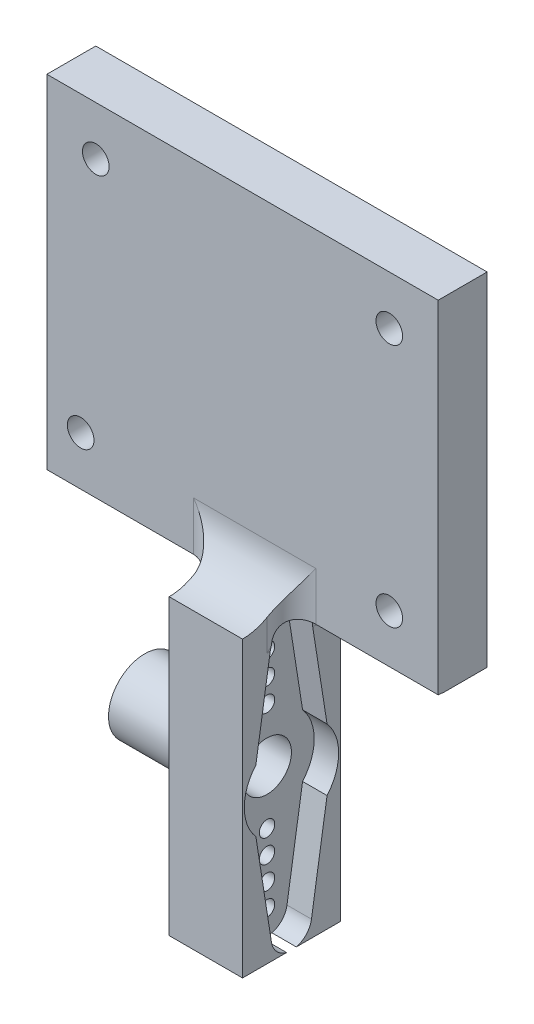
SolidWorks part; units mm, degrees
ref_plane "Front Plane" through (0, 0, 0) normal (0, 0, 1) x (1, 0, 0)
ref_plane "Top Plane" through (0, 0, 0) normal (0, 1, 0) x (1, 0, 0)
ref_plane "Right Plane" through (0, 0, 0) normal (1, 0, 0) x (0, 0, -1)
sketch "Sketch2" plane through (0, 0, 0) normal (1, 0, 0) x (0, 0, -1)
  line L0 (0, 0) -> (36.5165, 0) construction
  line L1 (-6.35, -19.05) -> (6.35, -19.05)
  line L2 (-6.35, -19.05) -> (-6.35, 19.05)
  line L3 (-6.35, 19.05) -> (6.35, 19.05)
  line L4 (6.35, -19.05) -> (6.35, 19.05)
  line L5 (-6.35, -19.05) -> (6.35, 19.05) construction
  line L6 (-6.35, 19.05) -> (6.35, -19.05) construction
  circle A0 centre (0, 0) radius 3.175
  point P0 (0, 0)
  point P8 (0, 0)
  dimension "D3" = 6.35
  dimension "D1" = 12.7
  dimension "D2" = 38.1
extrude "Boss-Extrude1" add sketch "Sketch2" along normal blind 9.525
sketch "Sketch3" plane through (0, 0, 0) normal (-1, 0, 0) x (0, 0, 1)
  circle A0 centre (0, 0) radius 4.699
  dimension "D1" = 9.398
extrude "Boss-Extrude2" add sketch "Sketch3" along normal blind 9.525
ref_plane "Plane1" through (3.175, 0, 0) normal (1, 0, 0) x (0, 0, -1)
sketch "Sketch6" plane through (3.175, 0, 0) normal (1, 0, 0) x (0, 0, -1)
  line L0 (6.35, 19.05) -> (-6.35, 19.05) construction
  line L1 (0, 19.05) -> (6.35, 19.05)
  line L2 (0, 19.05) -> (0, 63.5)
  line L3 (0, 63.5) -> (6.35, 63.5)
  line L4 (6.35, 19.05) -> (6.35, 63.5)
  point P4 (0, 0)
  point P5 (0, 0)
  point P7 (0, 19.05)
  dimension "D1" = 6.35
  dimension "D2" = 63.5
extrude "Boss-Extrude3" add sketch "Sketch6" along normal mid plane 50.8
fillet "Fillet1" radius 6.35 1 edges at (4.7625, 19.05, 0)
fillet "Fillet4" radius 3.175 4 edges at (0, 22.225, 0) (9.525, 22.225, 0) (9.525, 19.05, -3.175) (0, 19.05, -3.175)
sketch "Sketch7" plane through (9.525, 0, 0) normal (1, 0, 0) x (0, 0, -1)
  line L0 (2.5951, -16.9078) -> (4.6198, -4.0247)
  line L1 (4.6198, 4.0247) -> (2.5951, 16.9078)
  line L2 (-2.5951, 16.9078) -> (-4.6198, 4.0247)
  line L3 (-4.6198, -4.0247) -> (-2.5951, -16.9078)
  line L4 (2.4697, -16.8881) -> (4.5, -3.9686)
  line L5 (-4.5, -3.9686) -> (-2.4697, -16.8881)
  line L6 (-2.4697, 16.8881) -> (-4.5, 3.9686)
  line L7 (4.5, 3.9686) -> (2.4697, 16.8881)
  line L8 (2.4697, -16.8881) -> (4.5, -3.9686) construction
  line L9 (-4.5, -3.9686) -> (-2.4697, -16.8881) construction
  line L10 (-2.4697, 16.8881) -> (-4.5, 3.9686) construction
  line L11 (4.5, 3.9686) -> (2.4697, 16.8881) construction
  arc A0 (4.6198, -4.0247) -> (4.6198, 4.0247) centre (0, 0) ccw
  arc A1 (2.5951, 16.9078) -> (-2.5951, 16.9078) centre (0, 16.5) ccw
  arc A2 (-4.6198, 4.0247) -> (-4.6198, -4.0247) centre (0, 0) ccw
  arc A3 (-2.5951, -16.9078) -> (2.5951, -16.9078) centre (0, -16.5) ccw
  arc A4 (4.5, -3.9686) -> (4.5, 3.9686) centre (0, 0) ccw
  arc A5 (-2.4697, -16.8881) -> (2.4697, -16.8881) centre (0, -16.5) ccw
  arc A6 (-4.5, 3.9686) -> (-4.5, -3.9686) centre (0, 0) ccw
  arc A7 (2.4697, 16.8881) -> (-2.4697, 16.8881) centre (0, 16.5) ccw
  arc A8 (4.5, -3.9686) -> (4.5, 3.9686) centre (0, 0) ccw construction
  arc A9 (-2.4697, -16.8881) -> (2.4697, -16.8881) centre (0, -16.5) ccw construction
  arc A10 (-4.5, 3.9686) -> (-4.5, -3.9686) centre (0, 0) ccw construction
  arc A11 (2.4697, 16.8881) -> (-2.4697, 16.8881) centre (0, 16.5) ccw construction
  dimension "D2" = 0.127
sketch "Sketch8" plane through (9.525, 0, 0) normal (1, 0, 0) x (0, 0, -1)
  circle A0 centre (0, -16) radius 0.75 construction
  circle A3 centre (0, -13) radius 0.75 construction
  circle A4 centre (0, -10) radius 0.75 construction
  circle A5 centre (0, -7) radius 0.75 construction
  circle A6 centre (0, 16) radius 0.75 construction
  circle A7 centre (0, 13) radius 0.75 construction
  circle A8 centre (0, 10) radius 0.75 construction
  circle A9 centre (0, 7) radius 0.75 construction
  circle A10 centre (0, -16) radius 0.75 construction
  circle A11 centre (0, -13) radius 0.75 construction
  circle A12 centre (0, -10) radius 0.75 construction
  circle A13 centre (0, -7) radius 0.75 construction
  circle A14 centre (0, 16) radius 0.75 construction
  circle A15 centre (0, 13) radius 0.75 construction
  circle A16 centre (0, 10) radius 0.75 construction
  circle A17 centre (0, 7) radius 0.75 construction
  circle A18 centre (0, -16) radius 1.004
  circle A19 centre (0, -13) radius 1.004
  circle A20 centre (0, -10) radius 1.004
  circle A21 centre (0, -7) radius 1.004
  circle A22 centre (0, 16) radius 1.004
  circle A23 centre (0, 13) radius 1.004
  circle A24 centre (0, 10) radius 1.004
  circle A25 centre (0, 7) radius 1.004
extrude "Cut-Extrude1" cut sketch "Sketch7" against normal blind 3.175 and the other way through all
extrude "Cut-Extrude2" cut sketch "Sketch8" against normal through all
sketch "Sketch9" plane through (0, 0, -6.35) normal (0, 0, -1) x (-1, 0, 0)
  line L13 (15.875, 25.4) -> (15.875, 57.15)
  line L14 (3.175, 25.4) -> (15.875, 25.4)
  line L15 (-22.225, 25.4) -> (-12.7, 25.4)
  line L16 (-22.225, 57.15) -> (-22.225, 25.4)
  line L17 (15.875, 57.15) -> (-22.225, 57.15)
  line L18 (15.875, 25.4) -> (15.875, 57.15) construction
  line L19 (3.175, 25.4) -> (15.875, 25.4) construction
  line L20 (-22.225, 25.4) -> (-12.7, 25.4) construction
  line L21 (-22.225, 57.15) -> (-22.225, 25.4) construction
  line L22 (15.875, 57.15) -> (-22.225, 57.15) construction
  circle A0 centre (-22.225, 57.15) radius 1.727
  circle A1 centre (15.875, 57.15) radius 1.727
  circle A2 centre (17.8398, 25.4) radius 1.727
  circle A3 centre (-22.225, 25.4) radius 1.727
  dimension "D2" = 3.454
extrude "Cut-Extrude3" cut sketch "Sketch9" against normal through all
equation "\"tightTol\"= 0.005in"
equation "\"normTol\"= 0.01in"
equation "\"looseTol\"= 0.02in"
equation "\"Fry height\"= 3 / 8"
equation "\"Fry spacing\"= 1 / 2"
equation "\"Potato width\"= \"Fry spacing\" * 4"
equation "\"Potato length\"= 3"
equation "\"D1@Sketch3\"=0.375000in-\"tightTol\""
equation "\"Plate rim width\"= 0.5"
equation "\"D2@Sketch6\"=2.000000in+\"Plate rim width\""
equation "\"D2@Sketch7\"=\"tightTol\""
equation "\"D1@Sketch8\"=\"normTol\""
equation "\"D2@Sketch9\"=3.2mm+\"normTol\""
